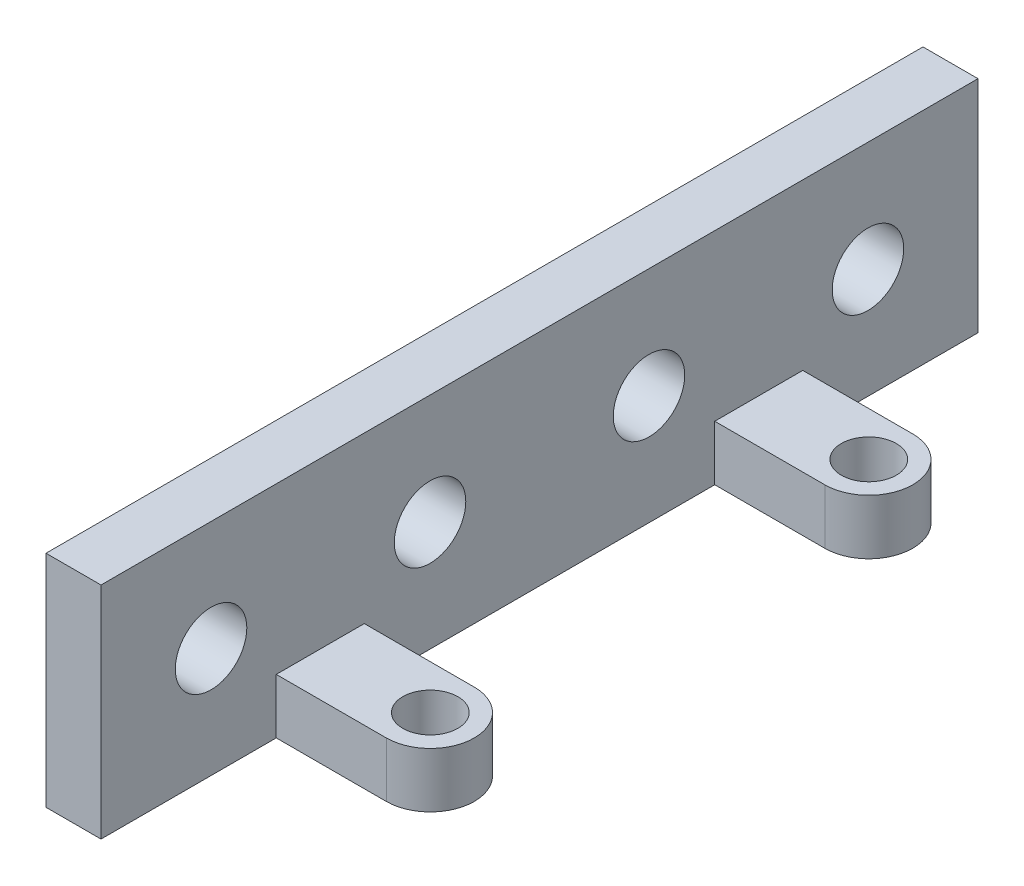
SolidWorks part; units mm, degrees
ref_plane "Front Plane" through (0, 0, 0) normal (0, 0, 1) x (1, 0, 0)
ref_plane "Top Plane" through (0, 0, 0) normal (0, 1, 0) x (1, 0, 0)
ref_plane "Right Plane" through (0, 0, 0) normal (1, 0, 0) x (0, 0, -1)
sketch "Sketch1" plane through (0, 0, 0) normal (1, 0, 0) x (0, 0, -1)
  line L1 (0, 0) -> (-79.7, 0)
  line L2 (0, 0) -> (0, 20)
  line L3 (0, 20) -> (-79.7, 20)
  line L4 (-79.7, 0) -> (-79.7, 20)
  circle A0 centre (-29.9, 10) radius 3.25
  circle A1 centre (-49.8, 10) radius 3.25
  circle A2 centre (-69.7, 10) radius 3.25
  circle A3 centre (-10, 10) radius 3.25
  point P11 (0, 0)
  dimension "D3" = 6.5
  dimension "D4" = 10
  dimension "D10" = 19.9
  dimension "D2" = 20
  dimension "D5" = 19.9
  dimension "D6" = 10
  dimension "D7" = 10
  dimension "D8" = 10
  dimension "D9" = 19.9
  dimension "D11" = 10
  dimension "D12" = 10
extrude "Boss-Extrude1" add sketch "Sketch1" along normal blind 5
sketch "Sketch2" plane through (5, 0, 0) normal (1, 0, 0) x (0, 0, -1)
  line L0 (-79.7, 0) -> (-39.85, 0)
  line L2 (-79.7, 0) -> (0, 0) construction
  line L3 (0, 20) -> (-79.7, 20) construction
  line L4 (-15.925, 5) -> (-23.925, 5)
  line L5 (-15.925, 0) -> (-15.925, 5)
  line L6 (-63.775, 0) -> (-55.775, 0)
  line L7 (-63.775, 0) -> (-63.775, 5)
  line L8 (-63.775, 5) -> (-55.775, 5)
  line L9 (-55.775, 5) -> (-55.775, 0)
  line L10 (-39.85, 0) -> (-39.85, 20) construction
  line L13 (-15.925, 0) -> (-23.925, 0)
  line L14 (-23.925, 5) -> (-23.925, 0)
  point P2 (-59.775, 0)
  point P3 (0, 0)
  point P5 (-59.775, 0)
  point P6 (0, 0)
  point P7 (-43.7965, 0)
  point P13 (0, 0)
  point P14 (-43.0862, 15.4462)
  point P18 (0, 0)
  point P19 (0, 0)
  dimension "D1" = 39.85
  dimension "D5" = 8
  dimension "D6" = 5
extrude "Boss-Extrude2" add sketch "Sketch2" along normal blind 10 contours L9 L6 L7 L8 | L4 L14 L13 L5
sketch "Sketch3" plane through (0, 5, 0) normal (0, 1, 0) x (1, 0, 0)
  line L0 (15, -55.775) -> (15, -63.775)
  arc A0 (15, -55.775) -> (15, -63.775) centre (15, -59.775) cw
  circle A1 centre (15, -59.775) radius 2.5
  dimension "D1" = 5
extrude "Boss-Extrude3" add sketch "Sketch3" against normal blind 5 contours A0 L0
extrude "Cut-Extrude2" cut sketch "Sketch3<6>" against normal through all contours A1
sketch "Sketch3<6>" plane through (0, 5, 0) normal (0, 1, 0) x (1, 0, 0) same geometry as "Sketch3"
ref_plane "Plane1" through (0, 0, 39.85) normal (0, 0, 1) x (1, 0, 0)
mirror "Mirror1" about plane through (0, 0, 39.85) normal (0, 0, 1) of "Boss-Extrude3", "Cut-Extrude2"
